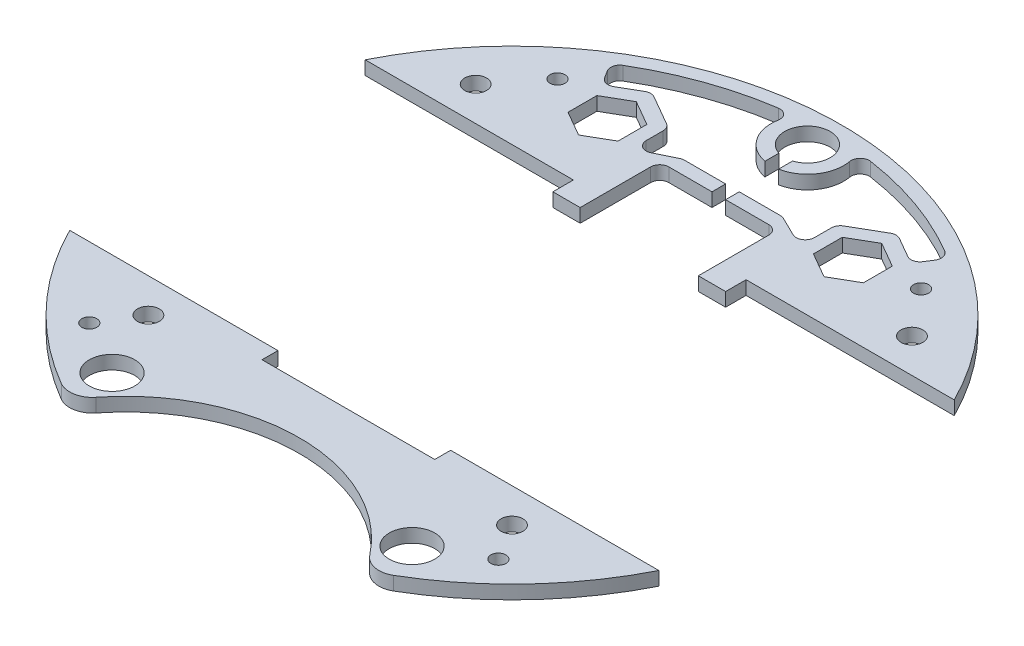
SolidWorks part; units mm, degrees
material "Acrylic (Medium-high impact)"
ref_plane "Front Plane" through (0, 0, 0) normal (0, 0, 1) x (1, 0, 0)
ref_plane "Top Plane" through (0, 0, 0) normal (0, 1, 0) x (1, 0, 0)
ref_plane "Right Plane" through (0, 0, 0) normal (1, 0, 0) x (0, 0, -1)
sketch "Sketch1" plane through (0, 0, 0) normal (0, 1, 0) x (1, 0, 0)
  line L0 (0, -85) -> (-32.4891, -64.8129) construction
  line L1 (0, -85) -> (0, 0) construction
  arc A0 (36.5434, -62.6165) -> (-36.5434, -62.6165) centre (0, 0) ccw
  arc A1 (30.0898, -61.3851) -> (-30.0898, -61.3851) centre (0, -85) ccw
  arc A2 (36.5434, -62.6165) -> (30.0898, -61.3851) centre (34.0231, -58.2982) cw
  arc A3 (-30.0898, -61.3851) -> (-36.5434, -62.6165) centre (-34.0231, -58.2982) cw
  dimension "D1" = 145
  dimension "D2" = 76.5
  dimension "D4" = 5
  dimension "D3" = 85
extrude "Boss-Extrude1" add sketch "Sketch1" along normal blind 3
sketch "solenoid placement" plane through (0, 3, 0) normal (0, 1, 0) x (1, 0, 0)
  line L4 (-19, -36) -> (19, -36)
  line L5 (-19, 28) -> (-19, -36)
  line L6 (19, 28) -> (-19, 28)
  line L7 (19, -36) -> (19, 28)
  line L8 (-19, -36) -> (19, -36)
  line L9 (-19, 28) -> (-19, -36)
  line L10 (19, 28) -> (-19, 28)
  line L11 (19, -36) -> (19, 28)
  dimension "D1" = 0
extrude "Cut-Extrude1" cut sketch "solenoid placement" against normal through all
sketch "Sketch5" plane through (0, 3, 0) normal (0, 1, 0) x (1, 0, 0)
  line L12 (-21.5, 51.1754) -> (-27, 54.3509)
  line L13 (-27, 54.3509) -> (-32.5, 51.1754)
  line L14 (-32.5, 51.1754) -> (-32.5, 44.8246)
  line L15 (-32.5, 44.8246) -> (-27, 41.6491)
  line L16 (-27, 41.6491) -> (-21.5, 44.8246)
  line L17 (-21.5, 44.8246) -> (-21.5, 51.1754)
  line L18 (-21.5, 51.1754) -> (-27, 54.3509)
  line L19 (-27, 54.3509) -> (-32.5, 51.1754)
  line L20 (-32.5, 51.1754) -> (-32.5, 44.8246)
  line L21 (-32.5, 44.8246) -> (-27, 41.6491)
  line L22 (-27, 41.6491) -> (-21.5, 44.8246)
  line L23 (-21.5, 44.8246) -> (-21.5, 51.1754)
  line L24 (21.5, 51.1754) -> (21.5, 44.8246)
  line L25 (21.5, 44.8246) -> (27, 41.6491)
  line L26 (27, 41.6491) -> (32.5, 44.8246)
  line L27 (32.5, 44.8246) -> (32.5, 51.1754)
  line L28 (32.5, 51.1754) -> (27, 54.3509)
  line L29 (27, 54.3509) -> (21.5, 51.1754)
  line L42 (21.5, 51.1754) -> (21.5, 44.8246)
  line L43 (21.5, 44.8246) -> (27, 41.6491)
  line L44 (27, 41.6491) -> (32.5, 44.8246)
  line L45 (32.5, 44.8246) -> (32.5, 51.1754)
  line L46 (32.5, 51.1754) -> (27, 54.3509)
  line L47 (27, 54.3509) -> (21.5, 51.1754)
  dimension "D1" = 0
  dimension "D2" = 0
extrude "Cut-Extrude5" cut sketch "Sketch5" against normal through all
sketch "Sketch6" plane through (0, 3, 0) normal (0, 1, 0) x (1, 0, 0)
  circle A0 centre (48, 40) radius 2.4
  circle A1 centre (40, -40) radius 2.4
  circle A2 centre (40, -40) radius 2.4 construction
  circle A3 centre (-40, -40) radius 2.4
  circle A4 centre (-40, -40) radius 2.4 construction
  circle A5 centre (48, 40) radius 2.4
  circle A6 centre (48, 40) radius 2.4 construction
  circle A7 centre (-48, 40) radius 2.4
  circle A8 centre (-48, 40) radius 2.4 construction
  circle A9 centre (-48, 40) radius 2.4
  circle A10 centre (40, -40) radius 2.4
  circle A11 centre (-40, -40) radius 2.4
  dimension "D5" = 4.8
extrude "Cut-Extrude6" cut sketch "Sketch6" against normal through all
sketch "Sketch3" plane through (0, 3, 0) normal (0, 1, 0) x (1, 0, 0)
  line L0 (-19, 28) -> (-19, 32.5)
  line L1 (72.5, -32.5) -> (-72.5, -32.5)
  line L2 (72.5, -32.5) -> (72.5, 32.5)
  line L3 (72.5, 32.5) -> (19, 32.5)
  line L4 (-72.5, -32.5) -> (-72.5, 32.5)
  line L5 (72.5, -32.5) -> (-72.5, 32.5) construction
  line L6 (72.5, 32.5) -> (-72.5, -32.5) construction
  line L7 (-19, 28) -> (19, 28)
  line L8 (19, 28) -> (19, 32.5)
  line L9 (-19, 32.5) -> (-72.5, 32.5)
  line L10 (-19, 28) -> (-19, -36) construction
  arc A0 (36.5434, -62.6165) -> (-36.5434, -62.6165) centre (0, 0) ccw construction
  point P0 (0, 0)
  dimension "D1" = 65
extrude "Cut-Extrude3" cut sketch "Sketch3" against normal through all
sketch "Sketch7" plane through (0, 3, 0) normal (0, 1, 0) x (1, 0, 0)
  line L8 (13, 28) -> (13, 43.5)
  line L9 (-13, 28) -> (13, 28)
  line L10 (-13, 43.5) -> (-13, 28)
  line L11 (11, 45.5) -> (-11, 45.5)
  line L28 (13, 28) -> (13, 43.5)
  line L29 (-13, 28) -> (13, 28)
  line L30 (-13, 43.5) -> (-13, 28)
  line L31 (11, 45.5) -> (-11, 45.5)
  arc A4 (-11, 45.5) -> (-13, 43.5) centre (-11, 43.5) ccw
  arc A5 (13, 43.5) -> (11, 45.5) centre (11, 43.5) ccw
  arc A14 (-11, 45.5) -> (-13, 43.5) centre (-11, 43.5) ccw
  arc A15 (13, 43.5) -> (11, 45.5) centre (11, 43.5) ccw
  dimension "D1" = 0
extrude "Cut-Extrude7" cut sketch "Sketch7" against normal through all
sketch "Sketch8" plane through (0, 3, 0) normal (0, 1, 0) x (1, 0, 0)
  line L0 (0, 0) -> (0, -21.9152) construction
  circle A1 centre (33, -55) radius 5
  circle A4 centre (-33, -55) radius 5
  dimension "D3" = 10
  dimension "D1" = 33
  dimension "D2" = 55
extrude "Cut-Extrude8" cut sketch "Sketch8" against normal through all
sketch "Sketch9" plane through (0, 3, 0) normal (0, 1, 0) x (1, 0, 0)
  line L0 (0, 0) -> (0, 65) construction
  line L1 (1.5, 0) -> (1.5, 60.2303)
  line L2 (-1.5, 0) -> (-1.5, 60.2303)
  line L3 (1.5, 0) -> (1.5, 65) construction
  line L4 (-1.5, 0) -> (-1.5, 65) construction
  arc A0 (1.5, 60.2303) -> (-1.5, 60.2303) centre (0, 65) ccw
  arc A1 (1.5, 0) -> (-1.5, 0) centre (0, 0) cw
  dimension "D1" = 10
  dimension "D2" = 65
  dimension "D3" = 1.5
  dimension "D4" = 1.5
extrude "Cut-Extrude9" cut sketch "Sketch9" against normal through all
sketch "Sketch10" plane through (0, 3, 0) normal (0, 1, 0) x (1, 0, 0)
  line L0 (0, 0) -> (0, -25.927) construction
  circle A0 centre (45, -48) radius 1.65
  circle A1 centre (-45, -48) radius 1.65
  circle A2 centre (40, 50) radius 1.65
  circle A3 centre (-40, 50) radius 1.65
  dimension "D3" = 3.3
  dimension "D1" = 45
  dimension "D2" = 48
  dimension "D4" = 40
  dimension "D5" = 50
extrude "Cut-Extrude10" cut sketch "Sketch10" against normal blind 10
sketch "Sketch11" plane through (0, 3, 0) normal (0, 1, 0) x (1, 0, 0)
  line L0 (-1.5, 48.5) -> (1.5, 48.5)
  line L1 (-15.6199, 46.236) -> (-11.4164, 48.2959)
  line L2 (11.4164, 48.2959) -> (15.6199, 46.236)
  line L3 (35.0267, 55.3973) -> (36.0573, 57.0273)
  line L4 (-35.0267, 55.3973) -> (-36.0573, 57.0273)
  line L11 (-18.5, 44.8246) -> (-18.5, 52.9075)
  line L12 (-18.5, 52.9075) -> (-27, 57.815)
  line L13 (-27, 57.815) -> (-34, 53.7735)
  line L14 (-18.5, 48.0319) -> (-18.5, 51.7528)
  line L15 (-19.5, 53.4848) -> (-26, 57.2376)
  line L16 (-28, 57.2376) -> (-32.3362, 54.7341)
  line L19 (-1.5, 48.5) -> (-11, 48.5)
  line L20 (-1.5, 48.5) -> (-10.5363, 48.5)
  line L22 (11, 48.5) -> (1.5, 48.5)
  line L23 (10.5363, 48.5) -> (1.5, 48.5)
  line L32 (34, 53.7735) -> (27, 57.815)
  line L33 (27, 57.815) -> (18.5, 52.9075)
  line L34 (18.5, 52.9075) -> (18.5, 44.8246)
  line L35 (32.3362, 54.7341) -> (28, 57.2376)
  line L36 (26, 57.2376) -> (19.5, 53.4848)
  line L37 (18.5, 51.7528) -> (18.5, 48.0319)
  arc A0 (-7.8724, 66.4231) -> (-10.1321, 68.7575) centre (-9.8405, 66.7788) ccw
  arc A1 (7.8724, 66.4231) -> (10.1321, 68.7575) centre (9.8405, 66.7788) cw
  arc A2 (2.4, 57.3685) -> (-2.4, 57.3685) centre (0, 65) ccw
  arc A3 (0, 57) -> (7.8724, 66.4231) centre (0, 65) ccw
  arc A4 (-7.8724, 66.4231) -> (0, 57) centre (0, 65) ccw
  arc A5 (62.1257, 31.1552) -> (-62.1257, 31.1552) centre (0, 0) ccw
  arc A6 (35.3852, 59.8175) -> (10.1321, 68.7575) centre (0, 0) ccw
  arc A7 (-10.1321, 68.7575) -> (-35.3852, 59.8175) centre (0, 0) ccw
  arc A8 (36.0573, 57.0273) -> (35.3852, 59.8175) centre (34.3669, 58.0962) ccw
  arc A9 (32.3362, 54.7341) -> (35.0267, 55.3973) centre (33.3362, 56.4661) ccw
  arc A10 (28, 57.2376) -> (26, 57.2376) centre (27, 55.5056) ccw
  arc A11 (19.5, 53.4848) -> (18.5, 51.7528) centre (20.5, 51.7528) ccw
  arc A12 (18.5, 48.0319) -> (15.6199, 46.236) centre (16.5, 48.0319) cw
  arc A13 (10.5363, 48.5) -> (11.4164, 48.2959) centre (10.5363, 46.5) cw
  arc A14 (-10.5363, 48.5) -> (-11.4164, 48.2959) centre (-10.5363, 46.5) ccw
  arc A15 (-18.5, 48.0319) -> (-15.6199, 46.236) centre (-16.5, 48.0319) ccw
  arc A16 (-18.5, 51.7528) -> (-19.5, 53.4848) centre (-20.5, 51.7528) ccw
  arc A17 (-26, 57.2376) -> (-28, 57.2376) centre (-27, 55.5056) ccw
  arc A18 (-32.3362, 54.7341) -> (-35.0267, 55.3973) centre (-33.3362, 56.4661) cw
  arc A19 (-36.0573, 57.0273) -> (-35.3852, 59.8175) centre (-34.3669, 58.0962) cw
  point P1 (0, 57.815)
  point P22 (2, 57.0231)
  point P27 (-6.8312, 69.1635)
  dimension "D7" = 2
  dimension "D1" = 3
  dimension "D2" = 3
  dimension "D3" = 3
  dimension "D4" = 3
  dimension "D5" = 3
  dimension "D6" = 3
extrude "Cut-Extrude11" cut sketch "Sketch11" against normal through all
equation "\"smallPulleyTeeth\"= 30"
equation "\"largePulleyTeeth\"= 30"
equation "\"eighthThick\"= 3.0mm"
equation "\"sixteenthThick\" = 1.7mm"
equation "\"quarterThick\"=6.0mm"
equation "\"OD\" = 145mm"
equation "\"puckAngle\" = 60.5deg"
equation "\"D1@Sketch1\"=\"OD\""
equation "\"puckDiam\" = 76.5mm"
equation "\"D2@Sketch1\"=\"puckDiam\""
equation "\"D1@Boss-Extrude1\"=\"eighthThick\""
equation "\"axlePress\" = 5.9mm"
equation "\"press\" = 0.2mm"
equation "\"wheelClear\" = 0.3mm"
equation "\"10-32clear\" = 4.8mm"
equation "\"6-32clear\" = 3.3mm"
equation "\"8-32clear\" = 4.0mm"
equation "\"wheelHeight\" = 22mm"
equation "\"wheelWell\" = 65mm"
equation "\"D1@Sketch3\"=\"wheelWell\""
equation "\"puckDist\" = 85mm"
equation "\"scoopFillet\" = 5mm"
equation "\"4-40clear\" = 3.0mm"
equation "\"D3@Sketch1\"=\"puckDist\""
equation "\"D4@Sketch1\"=\"scoopFillet\""
equation "\"10-32tap\" = 4.45mm"
equation "\"D5@Sketch6\"=\"10-32clear\""
equation "\"D3@Sketch10\"=\"6-32clear\""
